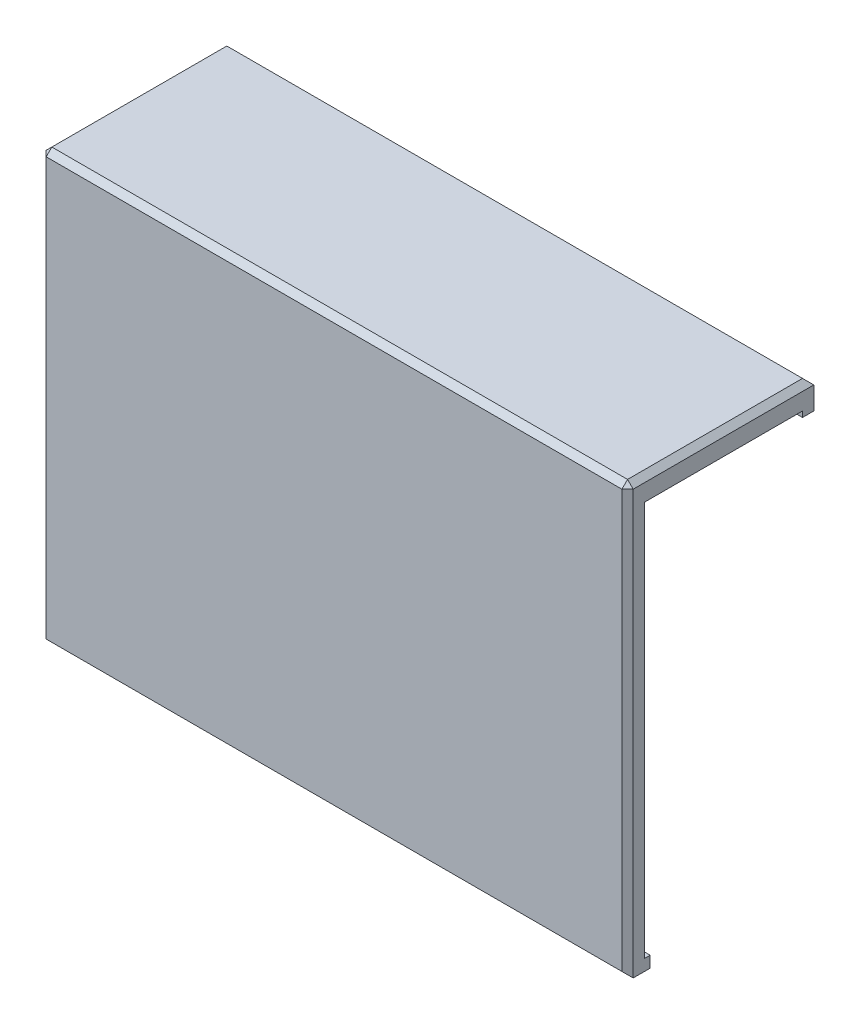
SolidWorks part; units mm, degrees
ref_plane "Front Plane" through (0, 0, 0) normal (0, 0, 1) x (1, 0, 0)
ref_plane "Top Plane" through (0, 0, 0) normal (0, 1, 0) x (1, 0, 0)
ref_plane "Right Plane" through (0, 0, 0) normal (1, 0, 0) x (0, 0, -1)
sketch "Sketch1" plane through (0, 0, 0) normal (0, 0, 1) x (1, 0, 0)
  line L0 (-2, -2) -> (-2, 74)
  line L1 (0, 0) -> (100, 0)
  line L2 (0, 0) -> (0, 72)
  line L3 (0, 72) -> (100, 72)
  line L4 (100, 0) -> (100, 72)
  line L5 (-2, 74) -> (102, 74)
  line L6 (102, -2) -> (102, 74)
  line L7 (-2, -2) -> (102, -2)
  line L8 (100, 0) -> (102, 0)
  line L9 (0, 0) -> (-2, 0)
  dimension "D1" = 72
  dimension "D2" = 100
  dimension "D3" = 2
extrude "Boss-Extrude1" add sketch "Sketch1" along normal blind 1 contours L1 L4 L3 L2 | L0 L7 L6 L5 L4 L1 L2 L3 region at (-0.7236, 37, 0) region at (50, 36, 0)
extrude "Boss-Extrude2" add sketch "Sketch1<3>" against normal blind 2 contours L9 L2 L3 L4 L8 L6 L5 L0 region at (-0.7236, 37, 0)
sketch "Sketch1<3>" plane through (0, 0, 0) normal (0, 0, 1) x (1, 0, 0) same geometry as "Sketch1"
sketch "Sketch2" plane through (0, 0, -2) normal (0, 0, -1) x (-1, 0, 0)
  line L0 (-102, 74) -> (2, 74)
  line L4 (2, 74) -> (2, 70)
  line L5 (2, 70) -> (0, 70)
  line L7 (0, 70) -> (0, 72)
  line L8 (0, 72) -> (-100, 72)
  line L10 (-100, 72) -> (-100, 70)
  line L12 (-100, 70) -> (-102, 70)
  line L13 (-102, 70) -> (-102, 74)
  point P2 (0, 0)
  point P4 (0, 0)
  point P6 (0, 0)
  point P7 (0, 0)
  point P14 (0, 0)
  point P20 (0, 0)
  point P21 (0, 0)
  point P22 (0, 0)
  dimension "D1" = 4
  dimension "D2" = 2
extrude "Boss-Extrude3" add sketch "Sketch2" along normal blind 28
sketch "Sketch3" plane through (0, 0, 0) normal (0, -1, 0) x (1, 0, 0)
  line L0 (-2, 1) -> (-2, -2) construction
  line L1 (-2, 1) -> (102, 1)
  line L2 (-2, 1) -> (-2, -3)
  line L3 (-2, -3) -> (102, -3)
  line L4 (102, 1) -> (102, -3)
  line L5 (-2, 1) -> (102, 1) construction
  line L6 (102, 1) -> (102, -2) construction
  dimension "D1" = 4
extrude "Boss-Extrude4" add sketch "Sketch3" along normal blind 2
sketch "Sketch4" plane through (-2, 0, 0) normal (-1, 0, 0) x (0, 0, 1)
  line L0 (-3, 0) -> (0.2, 0)
  line L1 (-2, 0) -> (-3, 0) construction
  line L2 (-3, -2) -> (-3, 0) construction
  arc A0 (0.2, 0) -> (-2.2, 0) centre (-1, 0) cw
  line M5 (-2, 0) -> (-3, 0)
  dimension "D2" = 1.2
  dimension "D1" = 3.2
extrude "Cut-Extrude1" cut sketch "Sketch4" against normal blind 11 and the other way blind 11 from offset 52 contours A0 L0 M5 region at (-2, -0.5093, -1) offset against normal yes
sketch "Sketch5" plane through (0, 0, -30) normal (0, 0, -1) x (-1, 0, 0)
  line L0 (-102, 74) -> (-102, 70) construction
  line L1 (-102, 74) -> (2, 74)
  line L2 (-102, 74) -> (-102, 69)
  line L3 (-102, 69) -> (2, 69)
  line L4 (2, 74) -> (2, 69)
  line L5 (2, 70) -> (2, 74) construction
  line L6 (2, 74) -> (-102, 74) construction
  dimension "D1" = 5
extrude "Boss-Extrude6" add sketch "Sketch5" along normal blind 2
sketch "Sketch6" plane through (-2, 0, 0) normal (-1, 0, 0) x (0, 0, 1)
  line L0 (-30, 69) -> (-30, 72.2)
  line L1 (-30, 69) -> (-30, 70) construction
  line L2 (-32, 69) -> (-30, 69) construction
  arc A0 (-30, 72.2) -> (-30, 69.8) centre (-30, 71) ccw
  dimension "D2" = 1.2
  dimension "D1" = 3.2
extrude "Cut-Extrude2" cut sketch "Sketch6" along normal blind 11 from offset 32 contours L0 A0 region at (-2, 71, -30.5093) offset against normal yes
extrude "Cut-Extrude3" cut sketch "Sketch6<3>" against normal blind 11 from offset 72 contours L0 A0 region at (-2, 71, -30.5093) offset against normal yes
sketch "Sketch6<3>" plane through (-2, 0, 0) normal (-1, 0, 0) x (0, 0, 1) same geometry as "Sketch6"
chamfer "Chamfer2" distance 1 angle 45 7 edges at (50, 74, -32) (50, 74, 1) (-2, 74, -15.5) (-2, 36, 1) (50, -2, 1) (102, 36, 1) (102, 74, -15.5)
